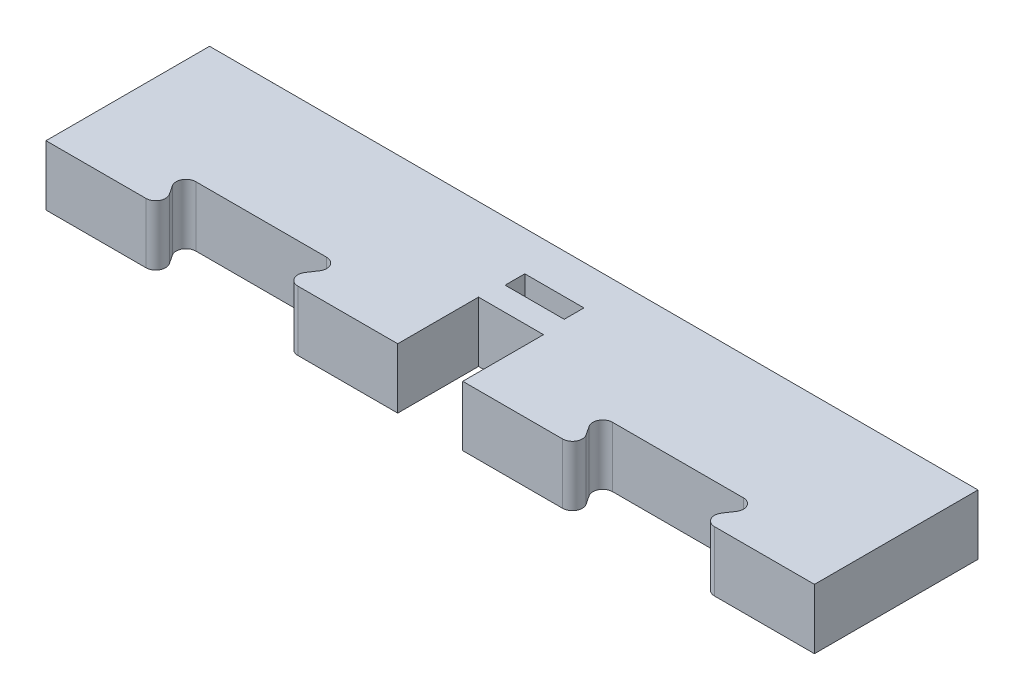
SolidWorks part; units mm, degrees
ref_plane "Front Plane" through (0, 0, 0) normal (0, 0, 1) x (1, 0, 0)
ref_plane "Top Plane" through (0, 0, 0) normal (0, 1, 0) x (1, 0, 0)
ref_plane "Right Plane" through (0, 0, 0) normal (1, 0, 0) x (0, 0, -1)
sketch "Sketch1" plane through (0, 0, 0) normal (0, 1, 0) x (1, 0, 0)
  line L0 (0, 0) -> (39, 0)
  line L1 (0, 0) -> (0, 8.3)
  line L2 (39, 0) -> (39, 8.3)
  line L3 (0, 8.3) -> (39, 8.3)
  dimension "D1" = 8.3
  dimension "D2" = 39
extrude "Boss-Extrude1" add sketch "Sketch1" along normal blind 3.05
sketch "Sketch2" plane through (0, 3.05, 0) normal (0, 1, 0) x (1, 0, 0)
  line L0 (0, 0) -> (0, 2)
  line L1 (0, 8.3) -> (0, 0) construction
  line L2 (0, 2) -> (39, 2) construction
  line L3 (39, 0) -> (39, 8.3) construction
  line L4 (0, 0) -> (6, 0)
  line L5 (0, 0) -> (39, 0) construction
  line L6 (6, 0) -> (4.675, 2)
  line L7 (4.675, 2) -> (13.175, 2)
  line L8 (13.175, 2) -> (11.85, 0)
  line L9 (11.85, 0) -> (27.15, 0)
  line L10 (27.15, 0) -> (25.825, 2)
  line L11 (25.825, 2) -> (34.325, 2)
  line L12 (34.325, 2) -> (33, 0)
  line L13 (33, 0) -> (39, 0)
  line L14 (6, 0) -> (11.85, 0)
  line L15 (27.15, 0) -> (33, 0)
  line L16 (0, 2) -> (4.675, 2)
  line L17 (34.325, 2) -> (39, 2)
  line L18 (39, 2) -> (39, 0)
  line M9 (0, 0) -> (39, 0)
  dimension "D1" = 2
  dimension "D2" = 6
  dimension "D3" = 4.675
  dimension "D4" = 8.5
extrude "Cut-Extrude1" cut sketch "Sketch2" against normal through all contours L8 L6 M9 | L12 L10 M9 region at (30.075, 3.05, -1.0616) region at (8.925, 3.05, -1.0616)
sketch "Sketch3" plane through (0, 3.05, 0) normal (0, 1, 0) x (1, 0, 0)
  line L0 (19.5, 8.3) -> (19.5, 6.3)
  line L1 (39, 8.3) -> (0, 8.3) construction
  line L2 (21, 6.3) -> (18, 6.3)
  line L3 (18, 6.3) -> (18, 5.3)
  line L4 (18, 5.3) -> (21, 5.3)
  line L5 (21, 5.3) -> (21, 6.3)
  line L6 (19.5, 5.3) -> (19.5, 4.1)
  line L7 (21.15, 4.1) -> (17.85, 4.1)
  line L8 (17.85, 4.1) -> (17.85, 0)
  line L9 (11.85, 0) -> (27.15, 0) construction
  line L10 (17.85, 0) -> (21.15, 0)
  line L11 (21.15, 0) -> (21.15, 4.1)
  point P7 (19.5, 6.3)
  point P14 (19.5, 4.1)
  line M9 (11.85, 0) -> (27.15, 0)
  dimension "D1" = 2
  dimension "D2" = 1
  dimension "D3" = 1.2
  dimension "D4" = 3.3
  dimension "D5" = 3
extrude "Cut-Extrude2" cut sketch "Sketch3" against normal through all contours L11 L7 L8 M9 | L4 L5 L2 L3 region at (19.5, 3.05, -5.8) region at (19.5, 3.05, -2.05)
fillet "Fillet1" radius 0.5 8 edges at (33, 1.525, 0) (27.15, 1.525, 0) (11.85, 1.525, 0) (6, 1.525, 0) (25.825, 1.525, -2) (34.325, 1.525, -2) (13.175, 1.525, -2) (4.675, 1.525, -2)
